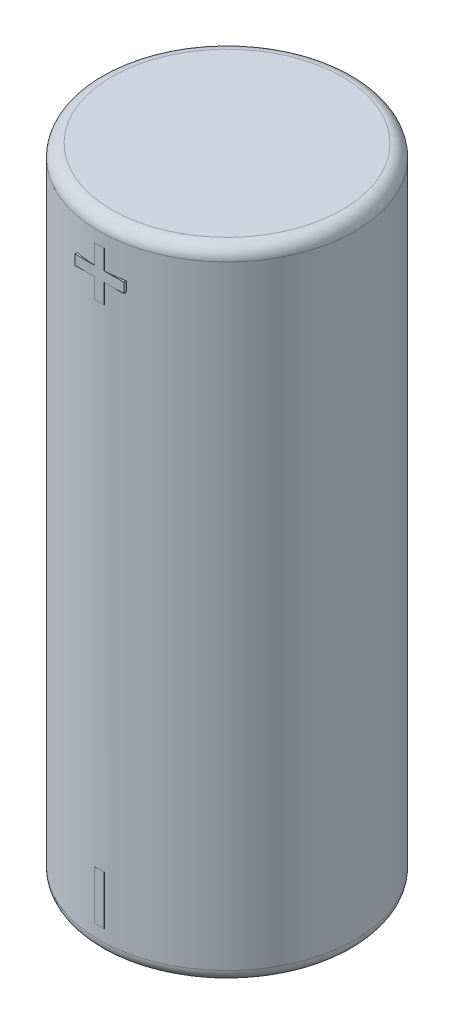
SolidWorks part; units mm, degrees
ref_plane "Front Plane" through (0, 0, 0) normal (0, 0, 1) x (1, 0, 0)
ref_plane "Top Plane" through (0, 0, 0) normal (0, 1, 0) x (1, 0, 0)
ref_plane "Right Plane" through (0, 0, 0) normal (1, 0, 0) x (0, 0, -1)
sketch "Sketch1" plane through (0, 0, 0) normal (0, 1, 0) x (1, 0, 0)
  circle A0 centre (0, 0) radius 13
  dimension "D1" = 26
extrude "Boss-Extrude1" add sketch "Sketch1" along normal blind 65
fillet "Fillet1" radius 1.27 1 edges at (0, 65, 13)
fillet "Fillet2" radius 1.27 1 edges at (0, 0, 13)
ref_plane "Plane1" through (0, 0, 13) normal (0, 0, 1) x (1, 0, 0)
sketch "Sketch2" plane through (0, 0, 13) normal (0, 0, 1) x (1, 0, 0)
  line L0 (11.73, 65) -> (-11.73, 65) construction
  line L1 (11.73, 65) -> (-11.73, 65)
  line L2 (0, 65) -> (0, 0) construction
  line L4 (-0.5, 62.5) -> (0.5, 62.5)
  line L5 (-0.5, 62.5) -> (-0.5, 57.5)
  line L6 (-0.5, 57.5) -> (0.5, 57.5)
  line L7 (0.5, 62.5) -> (0.5, 57.5)
  line L8 (-2.5, 60.5) -> (2.5, 60.5)
  line L9 (-2.5, 60.5) -> (-2.5, 59.5)
  line L10 (-2.5, 59.5) -> (2.5, 59.5)
  line L11 (2.5, 60.5) -> (2.5, 59.5)
  line L12 (-0.5, 7.5) -> (0.5, 7.5)
  line L13 (-0.5, 7.5) -> (-0.5, 2.5)
  line L14 (-0.5, 2.5) -> (0.5, 2.5)
  line L15 (0.5, 7.5) -> (0.5, 2.5)
  point P13 (0, 60)
  point P18 (0, 5)
  dimension "D1" = 5
  dimension "D2" = 5
  dimension "D3" = 1
  dimension "D4" = 1
  dimension "D5" = 0.5
  dimension "D6" = 2.5
  dimension "D7" = 5
  dimension "D8" = 0.5
  dimension "D9" = 2.5
  dimension "D10" = 1
  dimension "D11" = 5
  dimension "D12" = 5
  dimension "D13" = 2.5
  dimension "D14" = 0.5
extrude "Boss-Extrude2" add sketch "Sketch2" against normal blind 10 contours L2 L12 L13 L14 | L12 L2 L14 L15 | L5 L6 L7 L4 | L8 L11 L10 L9 region at (0.25, 5, 13) region at (-0.25, 5, 13)
